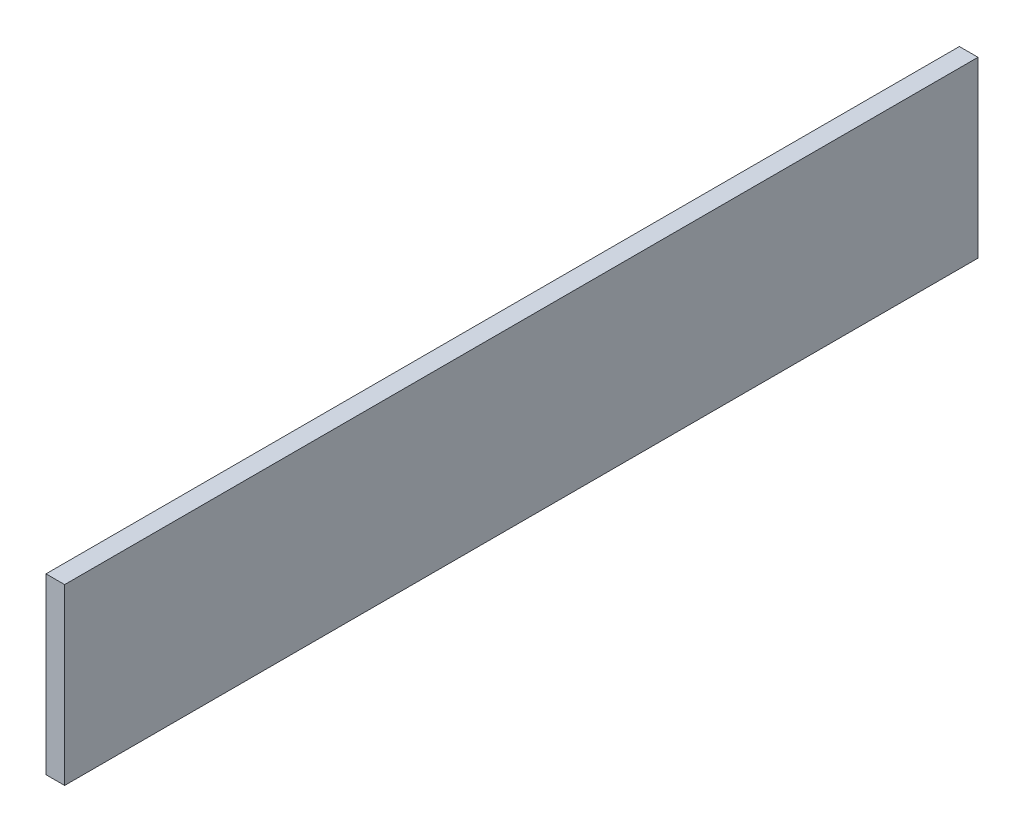
SolidWorks part; units mm, degrees
ref_plane "Front Plane" through (0, 0, 0) normal (0, 0, 1) x (1, 0, 0)
ref_plane "Top Plane" through (0, 0, 0) normal (0, 1, 0) x (1, 0, 0)
ref_plane "Right Plane" through (0, 0, 0) normal (1, 0, 0) x (0, 0, -1)
sketch "Sketch1" plane through (0, 0, 0) normal (1, 0, 0) x (0, 0, -1)
  line L1 (0, 0) -> (147, 0)
  line L2 (0, 0) -> (0, 28)
  line L3 (0, 28) -> (147, 28)
  line L4 (147, 0) -> (147, 28)
  dimension "D1" = 147
  dimension "D2" = 28
sheet metal parameters "Sheet-Metal1" thickness 3 parameters "D1"=0.7366
base flange "Base-Flange1" sketch "Sketch1" thickness 3 reverse thickness direction no parameters "D1"=0.7366
flat pattern "Flat-Pattern1" [suppressed]
sketch "Bend-Lines1" plane through (0, 0, 0) normal (0, 1, 0) x (1, 0, 0)
sketch3d "Bounding-Box1" [suppressed]
  line L0 (-144, 0, 0) -> (0, 0, 0) construction
  line L1 (-144, 28, 0) -> (0, 28, 0) construction
  line L2 (-144, 0, 0) -> (-144, 28, 0) construction
  line L3 (0, 0, 0) -> (0, 28, 0) construction
